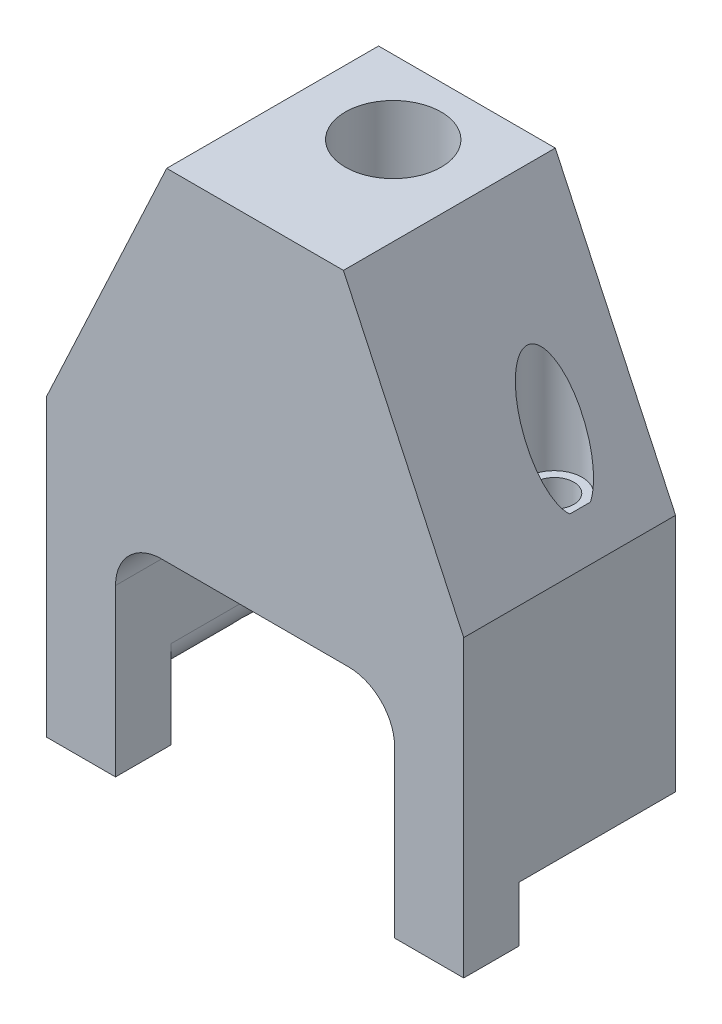
SolidWorks part; units mm, degrees
ref_plane "Front Plane" through (0, 0, 0) normal (0, 0, 1) x (1, 0, 0)
ref_plane "Top Plane" through (0, 0, 0) normal (0, 1, 0) x (1, 0, 0)
ref_plane "Right Plane" through (0, 0, 0) normal (1, 0, 0) x (0, 0, -1)
sketch "Sketch1" plane through (0, 0, 0) normal (0, 0, 1) x (1, 0, 0)
  line L0 (16.91, 0) -> (18.9, 0)
  line L2 (0, 1.76) -> (0, 6)
  line L3 (2.5, 8.5) -> (12.65, 8.5)
  line L4 (15.15, 1.76) -> (15.15, 6)
  line L5 (-3.75, 0) -> (-1.76, 0)
  line L6 (-3.75, 0) -> (-3.75, 27)
  line L7 (-3.75, 27) -> (18.9, 27)
  line L8 (18.9, 0) -> (18.9, 27)
  arc A0 (12.65, 8.5) -> (15.15, 6) centre (12.65, 6) cw
  arc A1 (0, 6) -> (2.5, 8.5) centre (2.5, 6) cw
  arc A2 (16.91, 0) -> (15.15, 1.76) centre (16.91, 1.76) cw
  arc A3 (-1.76, 0) -> (0, 1.76) centre (-1.76, 1.76) ccw
  point P9 (0, 8.5)
  point P16 (15.15, 0)
  point P19 (0, 0)
  dimension "D2" = 2.5
  dimension "D7" = 1.76
  dimension "D1" = 8.5
  dimension "D3" = 15.15
  dimension "D4" = 3.75
  dimension "D5" = 3.75
  dimension "D6" = 27
extrude "Boss-Extrude1" add sketch "Sketch1" against normal blind 11.5 contours L7 L8 L0 A2 L4 A0 L3 A1 L2 A3 L5 L6
sketch "Sketch3" plane through (0, 27, 0) normal (0, 1, 0) x (1, 0, 0)
  line L0 (-3.75, 11.5) -> (18.9, 11.5) construction
  line L1 (7.575, 11.5) -> (7.575, 0) construction
  line L2 (-3.75, 0) -> (18.9, 0) construction
  circle A0 centre (-1.425, 7.25) radius 1.05
  circle A1 centre (16.575, 7.25) radius 1.05
  dimension "D2" = 9
  dimension "D3" = 2.1
  dimension "D1" = 4.25
extrude "Cut-Extrude1" cut sketch "Sketch3" against normal through all both and the other way through all
sketch "Sketch4" plane through (0, 0, 0) normal (0, -1, 0) x (1, 0, 0)
  line L0 (15.15, -11.5) -> (15.15, 0) construction
  line L1 (-3.75, 0) -> (0, 0)
  line L2 (-3.75, 0) -> (-3.75, -3)
  line L3 (-3.75, -3) -> (0, -3)
  line L4 (0, 0) -> (0, -3)
  line L5 (18.9, 0) -> (15.15, 0)
  line L6 (18.9, 0) -> (18.9, -3)
  line L7 (18.9, -3) -> (15.15, -3)
  line L8 (15.15, 0) -> (15.15, -3)
  line L9 (0, -11.5) -> (0, 0) construction
  dimension "D1" = 3
  dimension "D2" = 3
extrude "Boss-Extrude2" add sketch "Sketch4" along normal blind 3 and the other way blind 11.5 contours L5 L8 L7 L6 | L3 L4 L1 L2 region at (17.025, 0, -1.5)
sketch "Sketch5" plane through (0, 27, 0) normal (0, 1, 0) x (1, 0, 0)
  line L0 (7.575, 11.5) -> (7.575, 0) construction
  line L1 (-3.75, 11.5) -> (18.9, 11.5) construction
  line L2 (-3.75, 0) -> (18.9, 0) construction
  circle A0 centre (7.575, 7.5) radius 1.25
  dimension "D1" = 2.5
  dimension "D2" = 4
extrude "Cut-Extrude2" cut sketch "Sketch5" against normal through all both and the other way through all contours A0
chamfer "Chamfer1" distance 14 angle 25 1 edges at (-3.75, 27, -5.75) first distance on face at (-3.75, 8, -4.8333)
chamfer "Chamfer2" distance 14 angle 25 1 edges at (18.9, 27, -5.75) first distance on face at (18.9, 8, -4.8333)
sketch "Sketch6" plane through (0, 27, 0) normal (0, 1, 0) x (1, 0, 0)
  circle A0 centre (7.575, 7.5) radius 2.6
  dimension "D1" = 5.2
extrude "Cut-Extrude3" cut sketch "Sketch6" against normal blind 5
sketch "Sketch7" plane through (0, 27, 0) normal (0, 1, 0) x (1, 0, 0)
  circle A0 centre (-1.425, 7.25) radius 1.5
  circle A1 centre (16.575, 7.25) radius 1.5
  dimension "D1" = 3
  dimension "D2" = 3
extrude "Cut-Extrude4" cut sketch "Sketch7" against normal blind 12
